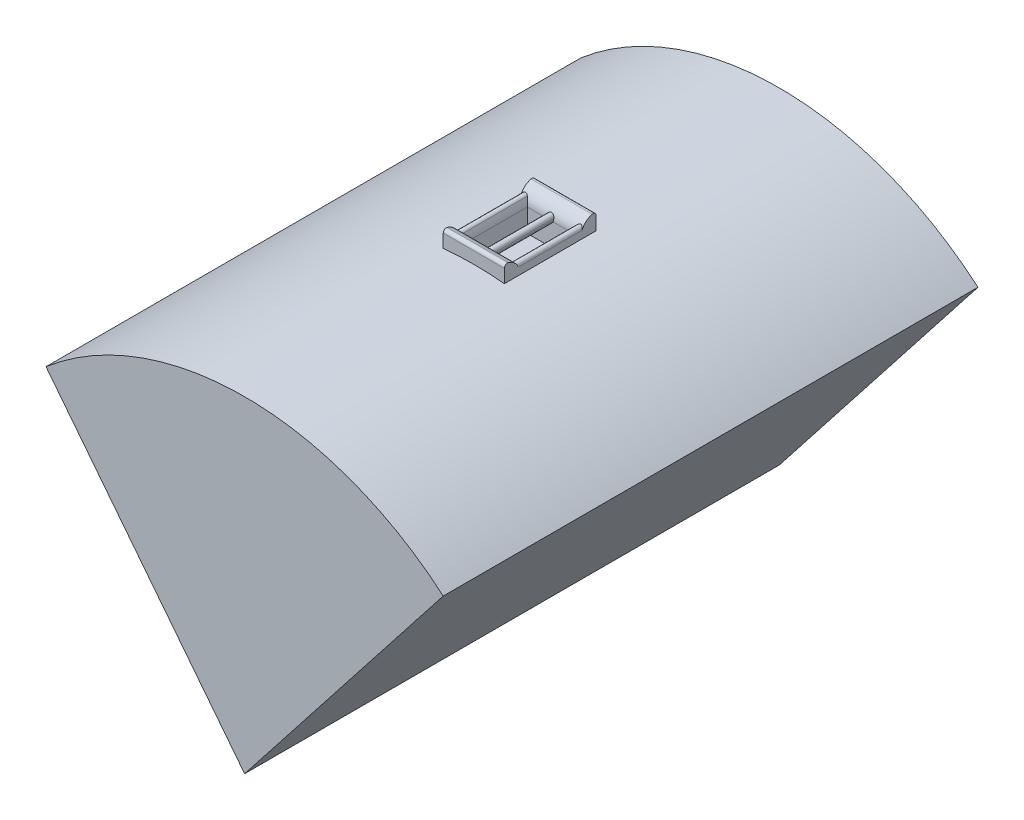
SolidWorks part; units mm, degrees
ref_plane "前视基准面" through (0, 0, 0) normal (0, 0, 1) x (1, 0, 0)
ref_plane "上视基准面" through (0, 0, 0) normal (0, 1, 0) x (1, 0, 0)
ref_plane "右视基准面" through (0, 0, 0) normal (1, 0, 0) x (0, 0, -1)
sketch "草图1" plane through (0, 0, 0) normal (0, 0, 1) x (1, 0, 0)
  line L1 (-50, 50) -> (50, 50)
  line L2 (-50, 50) -> (-50, -50)
  line L3 (-50, -50) -> (50, -50)
  line L4 (50, 50) -> (50, -50)
  circle A0 centre (0, 0) radius 200
  dimension "D1" = 400
  dimension "D2" = 100
  dimension "D3" = 100
  dimension "D4" = 50
  dimension "D5" = 50
extrude "凸台-拉伸1" add sketch "草图1" along normal blind 350
sketch "草图2" plane through (0, 0, 0) normal (0, 1, 0) x (1, 0, 0)
  line L1 (-289.6009, 53.8255) -> (334.4686, 53.8255)
  line L2 (-289.6009, 53.8255) -> (-289.6009, -430.7461)
  line L3 (-289.6009, -430.7461) -> (334.4686, -430.7461)
  line L4 (334.4686, 53.8255) -> (334.4686, -430.7461)
  line L5 (-130, 19.5628) -> (130, 19.5628)
  line L6 (-130, 19.5628) -> (-130, -388.3257)
  line L7 (-130, -388.3257) -> (130, -388.3257)
  line L8 (130, 19.5628) -> (130, -388.3257)
  dimension "D1" = 260
  dimension "D2" = 130
extrude "切除-拉伸1" cut sketch "草图2" against normal through all both and the other way through all
sketch "草图3" plane through (0, 0, 0) normal (0, 0, -1) x (-1, 0, 0)
  line L1 (-150.5303, 0) -> (181.2838, 0)
  line L2 (-150.5303, 0) -> (-150.5303, -218.7815)
  line L3 (-150.5303, -218.7815) -> (181.2838, -218.7815)
  line L4 (181.2838, 0) -> (181.2838, -218.7815)
extrude "切除-拉伸2" cut sketch "草图3" against normal through all
sketch "草图4" plane through (0, 0, 0) normal (0, 0, -1) x (-1, 0, 0)
  line L0 (-50, 50) -> (-130, 151.9868)
  line L1 (-130, 151.9868) -> (-177.073, -72.1432)
  line L2 (-177.073, -72.1432) -> (231.9888, -41.0483)
  line L3 (231.9888, -41.0483) -> (130, 151.9868)
  line L4 (130, 151.9868) -> (50, 50)
  line L5 (50, 50) -> (-50, 50)
extrude "切除-拉伸3" cut sketch "草图4" against normal blind 350
shell "抽壳1" thickness 5 removed face at (0, 112.9967, 0)
sketch "草图5" plane through (0, 0, 0) normal (0, 0, -1) x (-1, 0, 0)
  arc A0 (130, 151.9868) -> (-130, 151.9868) centre (0, 0) ccw construction
  point P0 (0, 200)
ref_plane "基准面1" through (0, 200, 0) normal (0, 1, 0) x (1, 0, 0)
sketch "草图6" plane through (0, 200, 0) normal (0, 1, 0) x (1, 0, 0)
  line L0 (0, 0) -> (0, -283.4536) construction
  line L1 (130, 0) -> (-130, 0) construction
  line L2 (-20, -140) -> (20, -140)
  line L3 (-20, -140) -> (-20, -200)
  line L4 (-20, -200) -> (20, -200)
  line L5 (20, -140) -> (20, -200)
  dimension "D1" = 40
  dimension "D2" = 60
  dimension "D3" = 20
  dimension "D4" = 140
extrude "凸台-拉伸2" add sketch "草图6" against normal blind 20 and the other way blind 10
sketch "草图7" plane through (0, 210, 0) normal (0, 1, 0) x (1, 0, 0)
  line L0 (-20, -140) -> (-20, -200) construction
  line L1 (-15, -150) -> (15, -150)
  line L2 (-15, -150) -> (-15, -190)
  line L3 (-15, -190) -> (15, -190)
  line L4 (15, -150) -> (15, -190)
  line L5 (-20, -200) -> (20, -200) construction
  dimension "D1" = 30
  dimension "D2" = 40
  dimension "D3" = 5
  dimension "D4" = 10
extrude "切除-拉伸4" cut sketch "草图7" against normal blind 25
chamfer "倒角2" distance 15 angle 45 1 edges at (0, 180, 140)
sketch "草图8" plane through (0, 0, 150) normal (0, 0, 1) x (1, 0, 0)
  line L0 (0, 201.938) -> (0, 200.9514) construction
  line L1 (2.1573, 201.938) -> (2.1573, 200.9514)
  line L2 (-2.1573, 201.938) -> (-2.1573, 200.9514)
  arc A0 (2.1573, 201.938) -> (-2.1573, 201.938) centre (0, 201.938) ccw
  arc A1 (-2.1573, 200.9514) -> (2.1573, 200.9514) centre (0, 200.9514) ccw
  point P3 (0, 201.4447)
extrude "凸台-拉伸3" add sketch "草图8" along normal up to surface (40 mm away) up to face at (0, 197.5, 190)
fillet "圆角1" radius 10 4 edges at (0, 210, 190) (15, 210, 170) (-15, 210, 170) (0, 210, 150)
fillet "圆角2" radius 2 4 edges at (0, 210, 200) (20, 208.6603, 170) (0, 210, 140) (-20, 208.6603, 170)
sketch "草图9" plane through (0, 0, 0) normal (0, 0, -1) x (-1, 0, 0)
  line L0 (-47.5673, 55) -> (0, -5.6405)
  line L3 (0, -5.6405) -> (47.761, 55.2469)
  line L4 (47.761, 55.2469) -> (-47.5673, 55)
  line L5 (-47.5673, 55) -> (-123.0718, 151.2558) construction
  line L6 (123.0718, 151.2558) -> (47.5673, 55) construction
  line L8 (123.0718, 151.2558) -> (47.5673, 55) construction
  line L9 (-47.5673, 55) -> (-123.0718, 151.2558) construction
  line L10 (-47.5673, 55) -> (47.5673, 55) construction
  point P2 (32.0292, 35.1914)
  point P8 (-30.9502, 33.8159)
  point P10 (61.8955, 73.266)
  point P13 (47.761, 55.2469)
  point P14 (-47.5673, 55)
  point P19 (29.0224, 31.3582)
extrude "切除-拉伸5" cut sketch "草图9" against normal through all
sketch "草图10" plane through (0, 0, 350) normal (0, 0, 1) x (1, 0, 0)
  line L0 (-50, 50) -> (0, -13.7418)
  line L1 (0, -13.7418) -> (50, 50)
  line L2 (-43.6453, 50) -> (0, -5.6405)
  line L3 (0, -5.6405) -> (43.6453, 50)
  line L4 (47.5673, 55) -> (43.6453, 50) construction
  line L5 (-43.6453, 50) -> (-47.761, 55.2469) construction
  line L6 (-130, 151.9868) -> (-50, 50) construction
  line L7 (50, 50) -> (130, 151.9868) construction
  line L8 (-50, 50) -> (-43.6453, 50)
  line L9 (43.6453, 50) -> (50, 50)
extrude "凸台-拉伸4" add sketch "草图10" against normal up to surface (350 mm away) up to face at (0, 112.2803, 0)
sketch "草图11" plane through (0, 0, 350) normal (0, 0, 1) x (1, 0, 0)
  line L0 (-47.761, 55.2469) -> (47.5673, 55)
  line L1 (47.5673, 55) -> (0, -5.6405)
  line L2 (0, -5.6405) -> (-47.761, 55.2469)
extrude "凸台-拉伸5" add sketch "草图11" against normal up to surface (5 mm away) up to face at (-0.0484, 114.1257, 345)
